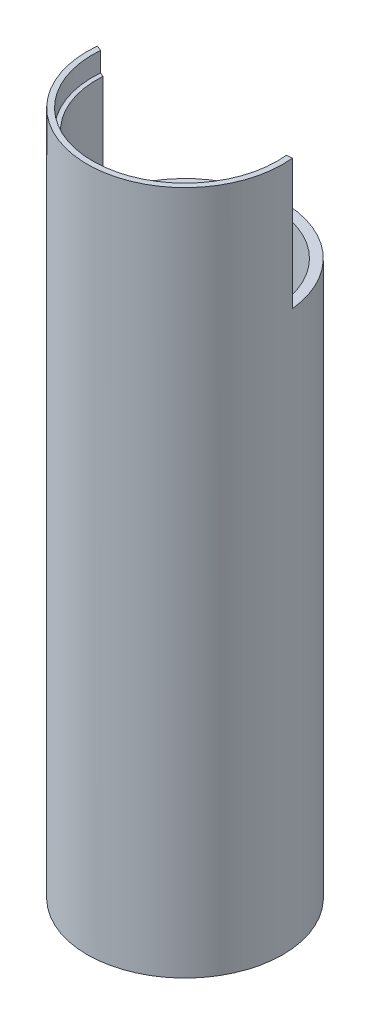
SolidWorks part; units mm, degrees
ref_plane "Front Plane" through (0, 0, 0) normal (0, 0, 1) x (1, 0, 0)
ref_plane "Top Plane" through (0, 0, 0) normal (0, 1, 0) x (1, 0, 0)
ref_plane "Right Plane" through (0, 0, 0) normal (1, 0, 0) x (0, 0, -1)
sketch "Sketch1" plane through (0, 0, 0) normal (0, 1, 0) x (1, 0, 0)
  circle A0 centre (0, 0) radius 15
extrude "Boss-Extrude1" add sketch "Sketch1" along normal blind 105
sketch "Sketch6" plane through (0, 0, 0) normal (0, -1, 0) x (1, 0, 0)
  circle A0 centre (0, 0) radius 14.222
extrude "Cut-Extrude4" cut sketch "Sketch6" along a picked direction on the side against the normal blind 3 contours A0
shell "Shell1" thickness 1.5 removed face at (0, 105, 15) removed face at (0, 3, -14.222)
sketch "Sketch8" plane through (0, 105, 0) normal (0, 1, 0) x (1, 0, 0)
  circle A0 centre (0, 0) radius 14.1573
extrude "Cut-Extrude6" cut sketch "Sketch8" against normal blind 3
sketch "Sketch9" plane through (0, 105, 0) normal (0, 1, 0) x (1, 0, 0)
  line L0 (14.9186, 1.5608) -> (13.4267, 1.4047)
  line L1 (13.4267, 1.4047) -> (-13.4708, 0.8881)
  line L2 (-13.4708, 0.8881) -> (-14.9255, 1.4929)
  arc A0 (-14.9255, 1.4929) -> (14.9186, 1.5608) centre (0, 0) cw
  circle A1 centre (0, 0) radius 15 construction
  circle A2 centre (0, 0) radius 13.5 construction
extrude "Cut-Extrude7" cut sketch "Sketch9" against normal blind 20
